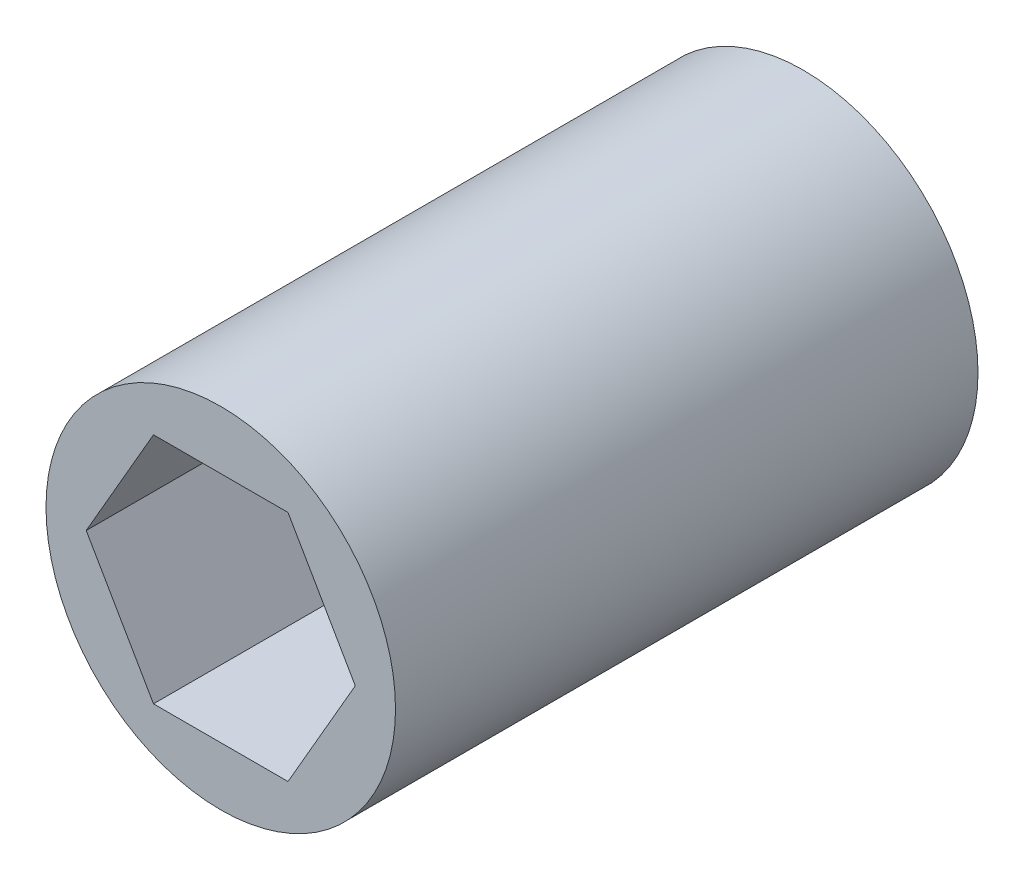
SolidWorks part; units mm, degrees
material "Nylon 101"
ref_plane "Front Plane" through (0, 0, 0) normal (0, 0, 1) x (1, 0, 0)
ref_plane "Top Plane" through (0, 0, 0) normal (0, 1, 0) x (1, 0, 0)
ref_plane "Right Plane" through (0, 0, 0) normal (1, 0, 0) x (0, 0, -1)
sketch "Sketch1" plane through (0, 0, 0) normal (0, 0, 1) x (1, 0, 0)
  line L1 (-3.6662, 6.35) -> (-7.3323, 0)
  line L2 (-7.3323, 0) -> (-3.6662, -6.35)
  line L3 (-3.6662, -6.35) -> (3.6662, -6.35)
  line L4 (3.6662, -6.35) -> (7.3323, 0)
  line L5 (7.3323, 0) -> (3.6662, 6.35)
  line L6 (3.6662, 6.35) -> (-3.6662, 6.35)
  circle A0 centre (0, 0) radius 6.35 construction
  circle A1 centre (0, 0) radius 9.525
  point P10 (0, 6.35)
  dimension "D1" = 12.7
  dimension "D2" = 19.05
extrude "Boss-Extrude1" add sketch "Sketch1" along normal blind 31.75
